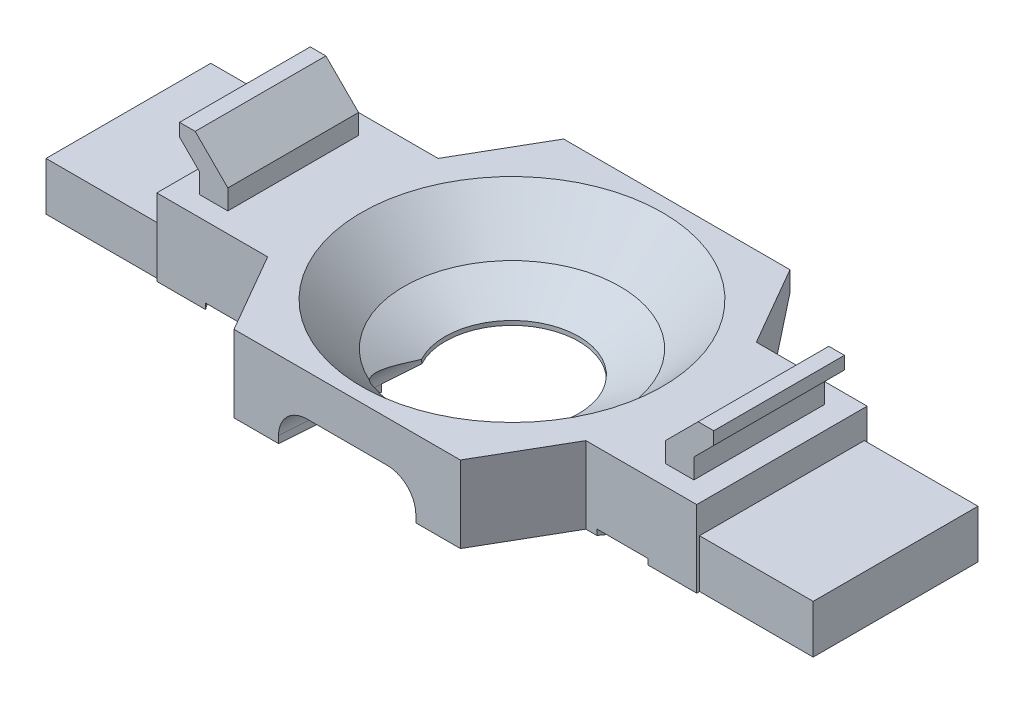
SolidWorks part; units mm, degrees
material "BioMed Black"
ref_plane "Front Plane" through (0, 0, 0) normal (0, 0, 1) x (1, 0, 0)
ref_plane "Top Plane" through (0, 0, 0) normal (0, 1, 0) x (1, 0, 0)
ref_plane "Right Plane" through (0, 0, 0) normal (1, 0, 0) x (0, 0, -1)
sketch "Sketch1" plane through (0, 0, 0) normal (0, 1, 0) x (1, 0, 0)
  line L0 (-13.5, -2.9) -> (-13.5, 2.9)
  line L1 (-13.5, 2.9) -> (-9.5, 2.9)
  line L2 (9.5, 2.9) -> (9.5, -2.9) construction
  line L3 (-5.6, 3) -> (-3.9834, 5.8)
  line L4 (-5.6, 3) -> (-5.6, -3) construction
  line L5 (-3.9834, 5.8) -> (0, 5.8)
  line L7 (0, 0) -> (0, 5.8) construction
  line L8 (0, 5.8) -> (3.9834, 5.8)
  line L9 (3.9834, 5.8) -> (5.6, 3)
  line L10 (9.5, 2.9) -> (13.5, 2.9)
  line L11 (13.5, 2.9) -> (13.5, -2.9)
  line L12 (13.5, -2.9) -> (9.5, -2.9)
  line L17 (-3.9834, -5.8) -> (-5.6, -3)
  line L19 (-9.5, -2.9) -> (-13.5, -2.9)
  line L20 (-13.5, 0) -> (13.5, 0) construction
  line L21 (-3.9834, -5.8) -> (3.9834, -5.8)
  line L22 (3.9834, -5.8) -> (5.6, -3)
  line L23 (9.5, -2.9) -> (9.5, -3)
  line L24 (9.5, -3) -> (5.6, -3)
  line L25 (9.5, 2.9) -> (9.5, 3)
  line L26 (9.5, 3) -> (5.6, 3)
  line L27 (5.6, 3) -> (5.6, -3) construction
  line L28 (-9.5, -2.9) -> (-9.5, 2.9) construction
  line L29 (-9.5, -2.9) -> (-9.5, -3)
  line L30 (-9.5, -3) -> (-5.6, -3)
  line L31 (-9.5, 2.9) -> (-9.5, 3)
  line L32 (-9.5, 3) -> (-5.6, 3)
  point P11 (5.6, 0)
  point P50 (13.5, 0)
  point P52 (0, 0)
  dimension "D3" = 60
  dimension "D4" = 7.9
  dimension "D1" = 5.8
  dimension "D2" = 5.8
  dimension "D5" = 0
  dimension "D6" = 13.5
  dimension "D7" = 13.5
  dimension "D8" = 0
  dimension "D9" = 0
  dimension "D10" = 60
  dimension "D11" = 60
  dimension "D12" = 7.9
  dimension "D13" = 5.8
  dimension "D14" = 5.8
  dimension "D15" = 4
  dimension "D16" = 6
  dimension "D18" = 4
  dimension "D19" = 0
  dimension "D23" = 60
extrude "Boss-Extrude1" add sketch "Sketch1" along normal blind 1.7 contours L22 L24 L23 L12 L11 L10 L25 L26 L9 L8 L5 L3 L32 L31 L1 L0 L19 L29 L30 L17 L21
sketch "Sketch4" plane through (-0.0261, 1.7, -0.212) normal (0, 1, 0) x (1, 0, 0)
  line L0 (9.5261, -3.212) -> (9.5261, 2.788)
  line L3 (9.5261, 2.788) -> (5.6261, 2.788)
  line L4 (5.6261, 2.788) -> (4.0095, 5.588)
  line L10 (-3.9573, 5.588) -> (-5.5739, 2.788)
  line L13 (-5.5739, 2.788) -> (-9.4739, 2.788)
  line L14 (-9.4739, 2.788) -> (-9.4739, -3.212)
  line L16 (-9.4739, -3.212) -> (-5.5739, -3.212)
  line L17 (-5.5739, -3.212) -> (-3.9573, -6.012)
  line L18 (-3.9573, -6.012) -> (4.0095, -6.012)
  line L19 (4.0095, -6.012) -> (5.6261, -3.212)
  line L21 (5.6261, -3.212) -> (9.5261, -3.212)
  line L27 (-9.4739, 2.788) -> (-5.5739, 2.788) construction
  line L28 (-5.5739, 2.788) -> (-3.9573, 5.588) construction
  line L30 (-9.4739, -3.212) -> (-5.5739, -3.212) construction
  line L34 (-3.9573, 5.588) -> (4.0095, 5.588)
extrude "Boss-Extrude2" add sketch "Sketch4" along normal blind 1
sketch "Sketch2" plane through (-0.0261, 0, -0.212) normal (0, -1, 0) x (1, 0, 0)
  circle A0 centre (0.0261, 0.212) radius 2.35
  dimension "D1" = 4.7
extrude "Cut-Extrude1" cut sketch "Sketch2" against normal through all
sketch "Sketch9" plane through (0, 0, 0) normal (0, 0, 1) x (1, 0, 0)
  line L0 (0, 0) -> (0, 2.7) construction
  line L5 (-3.9834, 2.7) -> (3.9834, 2.7) construction
  line L6 (5.3, 2.7) -> (3.8, 1.2)
  line L7 (3.8, 1.2) -> (2.35, 0.4)
  line L8 (2.35, 0.4) -> (2.35, 0)
  line L9 (6.38, 0) -> (-6.38, 0) construction
  line L10 (3.9834, 2.7) -> (5.6, 2.7) construction
  line L11 (0, 2.7) -> (5.3, 2.7)
  line L12 (2.35, 0) -> (0, 0)
  line L13 (0, 0) -> (0, 2.7)
  dimension "D1" = 5.3
  dimension "D2" = 2.35
  dimension "D3" = 0.4
  dimension "D4" = 45
  dimension "D5" = 0.8
revolve "Cut-Revolve1" cut sketch "Sketch9" angle 360 about L0
sketch "Sketch3" plane through (-0.0261, 0, -0.212) normal (0, -1, 0) x (1, 0, 0)
  circle A0 centre (0.0261, 0.212) radius 3.25
  dimension "D1" = 6.5
extrude "Cut-Extrude2" cut sketch "Sketch3" against normal blind 0.25
sketch "Sketch5" plane through (-0.0261, 0, -0.212) normal (0, -1, 0) x (1, 0, 0)
  line L0 (0.0261, 0.212) -> (2.0261, 0.212)
  line L1 (2.0261, 0.212) -> (2.5261, 7.212)
  line L2 (2.5261, 7.212) -> (-2.4739, 7.212)
  line L3 (-2.4739, 7.212) -> (-1.9739, 0.212)
  line L4 (-1.9739, 0.212) -> (0.0261, 0.212)
  line L5 (0.0261, 0.212) -> (0.0261, 7.212) construction
  dimension "D1" = 5
  dimension "D2" = 7
  dimension "D3" = 2
extrude "Cut-Extrude3" cut sketch "Sketch5" against normal blind 1.25
fillet "Fillet1" radius 1 2 edges at (-2.3194, 1.25, 4.4712) (2.3194, 1.25, 4.4712)
sketch "Sketch6" plane through (0, 0, 0) normal (0, 0, 1) x (1, 0, 0)
  line L0 (-9.4, 4.55) -> (-8.85, 4.55)
  line L1 (-8.7, 3.4) -> (-7.7, 3.4) construction
  line L2 (-8.7, 3.4) -> (-8.7, 1.7)
  line L3 (-8.7, 1.7) -> (-7.7, 1.7)
  line L4 (-7.7, 3.4) -> (-7.7, 1.7)
  line L5 (7.7, 3.4) -> (8.7, 3.4) construction
  line L6 (7.7, 3.4) -> (7.7, 1.7)
  line L7 (7.7, 1.7) -> (8.7, 1.7)
  line L8 (8.7, 3.4) -> (8.7, 1.7)
  line L10 (-9.4, 4.1) -> (-9.4, 4.55)
  line L15 (8.85, 4.55) -> (9.4, 4.55)
  line L16 (9.4, 4.1) -> (9.4, 4.55)
  line L17 (7.7, 3.4) -> (8.85, 4.55)
  line L18 (0, 0) -> (0, 3.4) construction
  line L19 (-13.5, 0) -> (13.5, 0) construction
  line L20 (-7.7, 3.4) -> (0, 3.4) construction
  line L21 (-8.85, 4.55) -> (8.85, 4.55) construction
  line L22 (-9.5, 2.7) -> (-5.6, 2.7) construction
  line L23 (-8.7, 3.4) -> (-9.4, 4.1)
  line L24 (-7.7, 3.4) -> (-8.85, 4.55)
  line L26 (8.7, 3.4) -> (9.4, 4.1)
  line L27 (0, 3.4) -> (7.7, 3.4) construction
  dimension "D1" = 0.45
  dimension "D2" = 15.4
  dimension "D3" = 45
  dimension "D4" = 0.7
  dimension "D5" = 1
  dimension "D6" = 0.7
  dimension "D7" = 1
  dimension "D8" = 45
  dimension "D9" = 0.7071
extrude "Boss-Extrude3" add sketch "Sketch6" along normal offset from surface 0.7 and the other way offset from surface 0.7 contours L10 L1 | L4 L1 L2 L3 | L16 L15 L5 | L8 L5 L6 L7 region at (-8.3908, 3.078, 0) region at (8.3908, 3.078, 0) up to face at (-7.55, 1.35, 3) other way up to face at (7.55, 1.35, -3)
sketch "Sketch8" plane through (-0.0261, 0, -0.212) normal (0, -1, 0) x (1, 0, 0)
  line L0 (13.5261, 0.212) -> (-13.4739, 0.212) construction
  line L5 (4.6113, 5.1248) -> (7.6701, 0.942)
  line L6 (4.6113, 5.1248) -> (5.784, 5.9824)
  line L7 (8.3688, 0.8335) -> (8.7343, 1.1008)
  line L8 (5.784, 5.9824) -> (8.8428, 1.7995)
  line L9 (4.6113, 5.1248) -> (9.1379, 1.3959) construction
  line L10 (7.9653, 0.5384) -> (5.784, 5.9824) construction
  line L11 (0.0261, 0.212) -> (0.0261, -5.588) construction
  line L12 (7.9653, -0.1144) -> (5.784, -5.5584) construction
  line L13 (4.6113, -4.7009) -> (9.1379, -0.972) construction
  line L14 (5.784, -5.5584) -> (8.8428, -1.3756)
  line L15 (8.3688, -0.4096) -> (8.7343, -0.6768)
  line L16 (4.6113, -4.7009) -> (5.784, -5.5584)
  line L17 (4.6113, -4.7009) -> (7.6701, -0.518)
  line L18 (-4.5591, -4.7009) -> (-9.0858, -0.972) construction
  line L19 (-7.9131, -0.1144) -> (-5.7318, -5.5584) construction
  line L20 (-7.9131, 0.5384) -> (-5.7318, 5.9824) construction
  line L21 (-4.5591, 5.1248) -> (-9.0858, 1.3959) construction
  line L22 (-4.5591, -4.7009) -> (-7.6179, -0.518)
  line L23 (-4.5591, -4.7009) -> (-5.7318, -5.5584)
  line L24 (-8.3167, -0.4096) -> (-8.6822, -0.6768)
  line L25 (-5.7318, -5.5584) -> (-8.7906, -1.3756)
  line L26 (-5.7318, 5.9824) -> (-8.7906, 1.7995)
  line L27 (-8.3167, 0.8335) -> (-8.6822, 1.1008)
  line L28 (-4.5591, 5.1248) -> (-5.7318, 5.9824)
  line L29 (-4.5591, 5.1248) -> (-7.6179, 0.942)
  arc A0 (8.7343, 1.1008) -> (8.8428, 1.7995) centre (8.4392, 1.5044) ccw
  arc A1 (8.3688, 0.8335) -> (7.6701, 0.942) centre (8.0737, 1.2371) cw
  arc A2 (8.3688, -0.4096) -> (7.6701, -0.518) centre (8.0737, -0.8132) ccw
  arc A3 (8.7343, -0.6768) -> (8.8428, -1.3756) centre (8.4392, -1.0804) cw
  arc A4 (-8.6822, -0.6768) -> (-8.7906, -1.3756) centre (-8.387, -1.0804) ccw
  arc A5 (-8.3167, -0.4096) -> (-7.6179, -0.518) centre (-8.0215, -0.8132) cw
  arc A6 (-8.3167, 0.8335) -> (-7.6179, 0.942) centre (-8.0215, 1.2371) ccw
  arc A7 (-8.6822, 1.1008) -> (-8.7906, 1.7995) centre (-8.387, 1.5044) cw
  dimension "D1" = 0.5
extrude "Cut-Extrude5" cut sketch "Sketch8" against normal blind 0.2
sketch "Sketch7" plane through (0, 0, 0) normal (1, 0, 0) x (0, 0, -1)
  line L0 (5.8, 2) -> (3.8, 0)
  line L1 (5.8, 2.7) -> (5.8, 0) construction
  line L2 (5.8, 0) -> (3, 0) construction
  line L3 (3.8, 0) -> (5.8, 0)
  line L4 (6.38, 0) -> (-6.38, 0) construction
  line L5 (5.8, 0) -> (5.8, 2)
  dimension "D1" = 45
  dimension "D2" = 2
extrude "Cut-Extrude4" cut sketch "Sketch7" along normal through all both and the other way through all
sketch "Sketch10" plane through (0, -2.3556, -3) normal (0, 0, -1) x (1, 0, 0)
  line L0 (9.1696, -2.8347) -> (5.8255, -2.8347) construction
  text T0 "v4" font "Century Gothic" height 2
extrude "VERZIO" cut sketch "Sketch10" against normal blind 0.2
